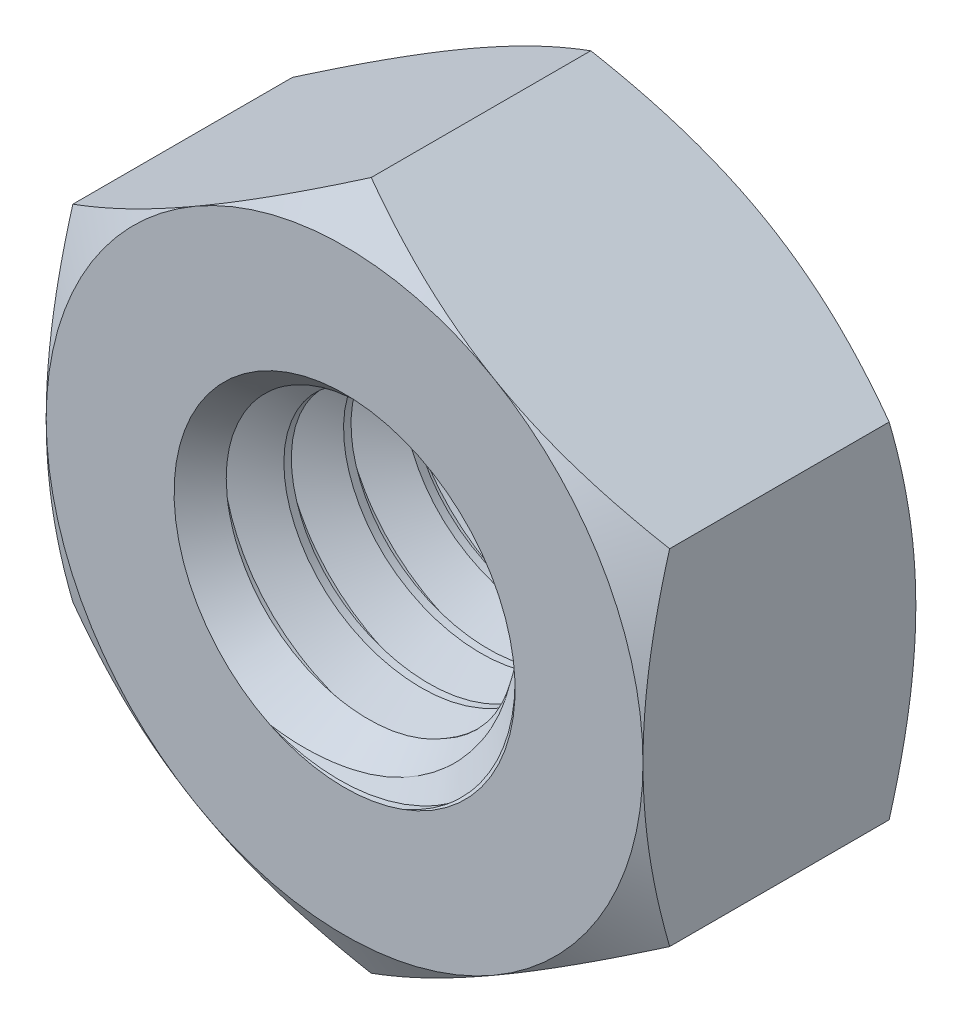
SolidWorks part; units mm, degrees
ref_plane "Front" through (0, 0, 0) normal (0, 0, 1) x (1, 0, 0)
ref_plane "Top" through (0, 0, 0) normal (0, 1, 0) x (1, 0, 0)
ref_plane "Right" through (0, 0, 0) normal (1, 0, 0) x (0, 0, -1)
sketch "Sketch1" plane through (0, 0, 0) normal (0, 0, 1) x (1, 0, 0)
  line L1 (-3.5, 2.0207) -> (-3.5, -2.0207)
  line L2 (-3.5, -2.0207) -> (0, -4.0415)
  line L3 (0, -4.0415) -> (3.5, -2.0207)
  line L4 (3.5, -2.0207) -> (3.5, 2.0207)
  line L5 (3.5, 2.0207) -> (0, 4.0415)
  line L6 (0, 4.0415) -> (-3.5, 2.0207)
  circle A0 centre (0, 0) radius 3.5 construction
  circle A1 centre (0, 0) radius 2 construction
  point P10 (0, 2)
  dimension "hex" = 7
  dimension "dia" = 4
extrude "Extrude1" add sketch "Sketch1" along normal mid plane 3.2
sketch "Sketch4" plane through (0, 0, -1.6) normal (0, 0, -1) x (-1, 0, 0)
  circle A0 centre (0, 0) radius 2 construction
  circle A1 centre (0, 0) radius 2
sketch "Sketch10" plane through (0, 0, 1.6) normal (0, 0, 1) x (1, 0, 0)
  circle A0 centre (0, 0) radius 2 construction
  circle A1 centre (0, 0) radius 2
extrude "Cut-Extrude2" cut sketch "Sketch10" against normal through all draft 45
sketch "Sketch11" plane through (0, 0, -1.6) normal (0, 0, -1) x (-1, 0, 0)
  circle A0 centre (0, 0) radius 2 construction
  circle A1 centre (0, 0) radius 2
extrude "Cut-Extrude3" cut sketch "Sketch11" against normal through all draft 45
sketch "Sketch13" plane through (0, 0, -1.6) normal (0, 0, -1) x (-1, 0, 0)
  circle A0 centre (0, 0) radius 2 construction
  circle A1 centre (0, 0) radius 2
extrude "Boss-Extrude1" add sketch "Sketch13" against normal up to vertex (3.2 mm away) separate body up to point (-3.5, 2.0207, 1.6)
curve "Helix/Spiral3" pitch 0.7 height 3.2 radius 2 left hand yes centre (0, 0, -1.6) axis (0, 0, 1) start towards (0, 1, 0)
sketch "Sketch12" plane through (0, 0, 0) normal (1, 0, 0) x (0, 0, -1)
  line L0 (2.2125, 2) -> (1.6, 2)
  line L1 (2.2125, 2) -> (1.95, 1.5453)
  line L2 (1.95, 1.5453) -> (1.8625, 1.5453)
  line L3 (1.8625, 1.5453) -> (1.6, 2)
  line L4 (1.9063, 1.5453) -> (1.9063, 2) construction
  line L5 (1.7313, 1.7727) -> (2.0813, 1.7727) construction
  dimension "D1" = 60
  dimension "D2" = 0.0875
  dimension "D3" = 0.35
sweep "Cut-Sweep1" cut profiles "Sketch12" path "Helix/Spiral3" align with end faces yes
combine bodies "Combine1" operation type subtract main body 116 bodies to subtract 118
sketch "Sketch7" plane through (0, 0, 1.6) normal (0, 0, 1) x (1, 0, 0)
  circle A0 centre (0, 0) radius 3.5 construction
  circle A1 centre (0, 0) radius 3.5
extrude "Extrude2" cut sketch "Sketch7" against normal blind 25.4 draft 60 flip side to cut
mirror "Mirror2" about plane through (0, 0, 0) normal (0, 0, 1) of "Extrude2"
sketch "Sketch8" plane through (0, 0, 1.6) normal (0, 0, 1) x (1, 0, 0)
  line L0 (-1.4142, 1.4142) -> (0, 0) construction
  line L1 (0, -2.0692) -> (0, 2.0692) construction
  circle A1 centre (0, 0) radius 2 construction
  point P0 (-1.4142, 1.4142)
  dimension "D1" = 45
sketch "Sketch14" plane through (0, 0, 1.6) normal (0, 0, 1) x (1, 0, 0)
  line L0 (0, 0) -> (-2, 0) construction
  arc A0 (-0.8737, -1.7991) -> (0.6746, -1.8828) centre (0, 0) ccw construction
equation "\"D3@Helix/Spiral3\" = \"length@Extrude1\" "
equation "\"D2@Sketch12\" = \"D4@Helix/Spiral3\"*.125"
equation "\"D3@Sketch12\" = \"D4@Helix/Spiral3\"*.50"
